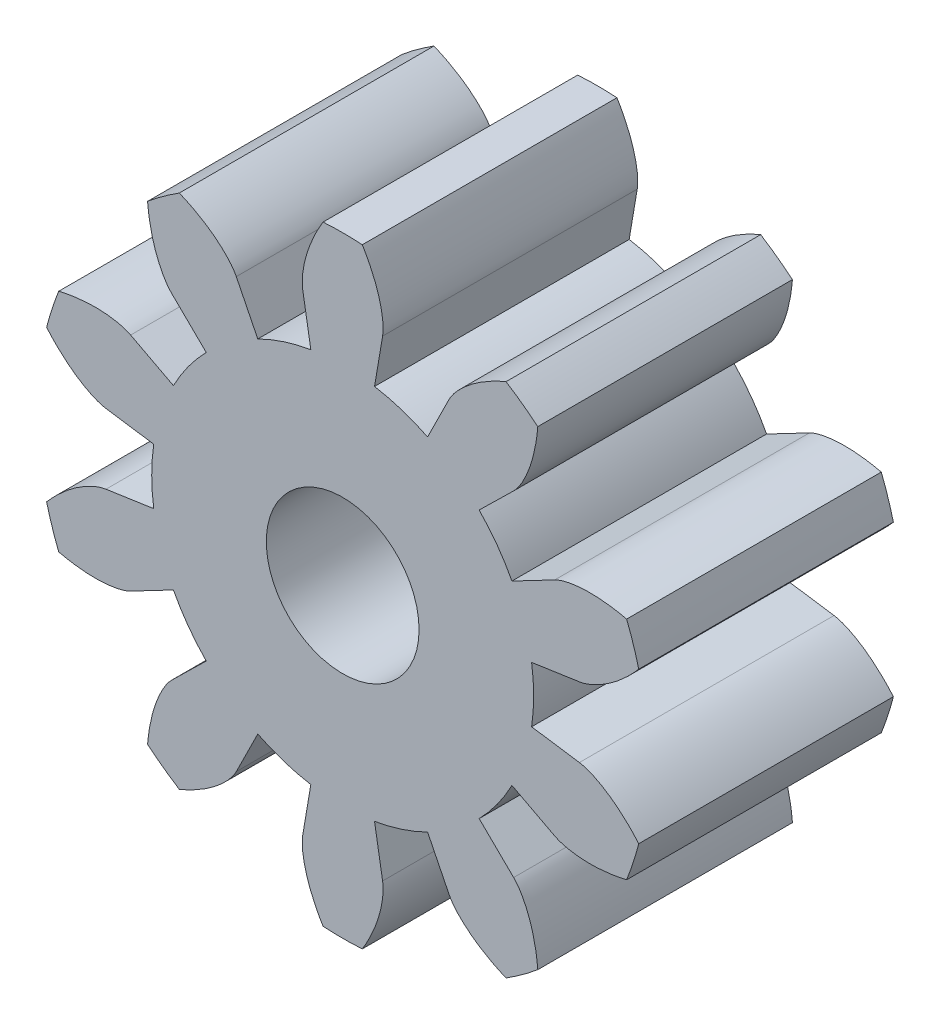
SolidWorks part; units mm, degrees
ref_plane "前视基准面" through (0, 0, 0) normal (0, 0, 1) x (1, 0, 0)
ref_plane "上视基准面" through (0, 0, 0) normal (0, 1, 0) x (1, 0, 0)
ref_plane "右视基准面" through (0, 0, 0) normal (1, 0, 0) x (0, 0, -1)
other "Configuration Table"
sketch "草图1" plane through (0, 0, 0) normal (0, 0, 1) x (1, 0, 0)
  line L0 (0, 0) -> (5, 0) construction
  line L1 (0, 0) -> (4.9384, 0.7822) construction
  line L2 (0, 0) -> (4.6481, 0.6862)
  line L3 (4.9384, 0.7822) -> (4.9384, -0.7822) construction
  line L4 (0, 0) -> (4.6481, -0.6862)
  circle A0 centre (0, 0) radius 6
  circle A1 centre (0, 0) radius 5 construction
  circle A2 centre (0, 0) radius 3.75
  circle A3 centre (0, 0) radius 4.6985 construction
  circle A4 centre (0, 0) radius 1.5
  spline S0 degree 4 poles (4.6481, 0.6862) (4.6835, 0.6914) (4.7813, 0.7134) (4.96, 0.7841) (5.2311, 0.9375) (5.5479, 1.1888) (5.9048, 1.5657) (6.2522, 2.0657) (6.551, 2.6636) (6.8384, 3.517) (6.9822, 4.4081) (6.9969, 5.3449) (6.862, 6.4517) (6.586, 7.5338) (6.0852, 8.7313) (5.3299, 9.9596) (4.4064, 11.0659) (3.3424, 12.0372) (2.1636, 12.8645) (0.8933, 13.5425) (-0.4466, 14.0687) (-1.6629, 14.396) (-2.6365, 14.5668) (-3.3507, 14.6476) (-3.7975, 14.6829) (-4.158, 14.7018) (-4.5134, 14.7121) (-4.8789, 14.7125) (-5.1964, 14.706) (-5.5003, 14.6924) (-5.8676, 14.6691) (-6.1207, 14.6466) (-6.5658, 14.6003) (-6.8589, 14.5561) (-7.1841, 14.508) (-7.4436, 14.4596) (-7.746, 14.4023) (-7.9471, 14.3573) (-8.0927, 14.3246) (-8.163, 14.308) knots 0 0 0 0 0 0.005604 0.015718 0.02996 0.048734 0.068727 0.096889 0.125051 0.153212 0.209535 0.237696 0.271429 0.327752 0.384075 0.440398 0.496721 0.553044 0.609367 0.66569 0.722013 0.778336 0.806497 0.820578 0.834659 0.84874 0.86282 0.876901 0.890982 0.900036 0.909091 0.931818 0.943182 0.954545 0.965909 0.977273 0.988636 1 1 1 1 1 construction
  spline S1 degree 4 poles (4.6481, 0.6862) (4.6835, 0.6914) (4.7813, 0.7134) (4.96, 0.7841) (5.2311, 0.9375) (5.5479, 1.1888) (5.9048, 1.5657) (6.2522, 2.0657) (6.551, 2.6636) (6.8384, 3.517) (6.9822, 4.4081) (6.9969, 5.3449) (6.862, 6.4517) (6.586, 7.5338) (6.0852, 8.7313) (5.3299, 9.9596) (4.4064, 11.0659) (3.3424, 12.0372) (2.1636, 12.8645) (0.8933, 13.5425) (-0.4466, 14.0687) (-1.6629, 14.396) (-2.6365, 14.5668) (-3.3507, 14.6476) (-3.7975, 14.6829) (-4.158, 14.7018) (-4.5134, 14.7121) (-4.8789, 14.7125) (-5.1964, 14.706) (-5.5003, 14.6924) (-5.7156, 14.6787) (-5.8219, 14.671) (-5.8742, 14.6669) knots 0 0 0 0 0 0.005604 0.015718 0.02996 0.048734 0.068727 0.096889 0.125051 0.153212 0.209535 0.237696 0.271429 0.327752 0.384075 0.440398 0.496721 0.553044 0.609367 0.66569 0.722013 0.778336 0.806497 0.820578 0.834659 0.84874 0.86282 0.876901 0.890982 0.900036 0.909091 0.909091 0.909091 0.909091 0.909091
  spline S2 degree 4 poles (4.6481, -0.6862) (4.6835, -0.6914) (4.7813, -0.7134) (4.96, -0.7841) (5.2311, -0.9375) (5.5479, -1.1888) (5.9048, -1.5657) (6.2522, -2.0657) (6.551, -2.6636) (6.8384, -3.517) (6.9822, -4.4081) (6.9969, -5.3449) (6.862, -6.4517) (6.586, -7.5338) (6.0852, -8.7313) (5.3299, -9.9596) (4.4064, -11.0659) (3.3424, -12.0372) (2.1636, -12.8645) (0.8933, -13.5425) (-0.4466, -14.0687) (-1.6629, -14.396) (-2.6365, -14.5668) (-3.3507, -14.6476) (-3.7975, -14.6829) (-4.158, -14.7018) (-4.5134, -14.7121) (-4.8789, -14.7125) (-5.1964, -14.706) (-5.5003, -14.6924) (-5.8676, -14.6691) (-6.1207, -14.6466) (-6.5658, -14.6003) (-6.8589, -14.5561) (-7.1841, -14.508) (-7.4436, -14.4596) (-7.746, -14.4023) (-7.9471, -14.3573) (-8.0927, -14.3246) (-8.163, -14.308) knots 0 0 0 0 0 0.005604 0.015718 0.02996 0.048734 0.068727 0.096889 0.125051 0.153212 0.209535 0.237696 0.271429 0.327752 0.384075 0.440398 0.496721 0.553044 0.609367 0.66569 0.722013 0.778336 0.806497 0.820578 0.834659 0.84874 0.86282 0.876901 0.890982 0.900036 0.909091 0.931818 0.943182 0.954545 0.965909 0.977273 0.988636 1 1 1 1 1 construction
  spline S3 degree 4 poles (4.6481, -0.6862) (4.6835, -0.6914) (4.7813, -0.7134) (4.96, -0.7841) (5.2311, -0.9375) (5.5479, -1.1888) (5.9048, -1.5657) (6.2522, -2.0657) (6.551, -2.6636) (6.8384, -3.517) (6.9822, -4.4081) (6.9969, -5.3449) (6.862, -6.4517) (6.586, -7.5338) (6.0852, -8.7313) (5.3299, -9.9596) (4.4064, -11.0659) (3.3424, -12.0372) (2.1636, -12.8645) (0.8933, -13.5425) (-0.4466, -14.0687) (-1.6629, -14.396) (-2.6365, -14.5668) (-3.3507, -14.6476) (-3.7975, -14.6829) (-4.158, -14.7018) (-4.5134, -14.7121) (-4.8789, -14.7125) (-5.1964, -14.706) (-5.5003, -14.6924) (-5.7156, -14.6787) (-5.8219, -14.671) (-5.8742, -14.6669) knots 0 0 0 0 0 0.005604 0.015718 0.02996 0.048734 0.068727 0.096889 0.125051 0.153212 0.209535 0.237696 0.271429 0.327752 0.384075 0.440398 0.496721 0.553044 0.609367 0.66569 0.722013 0.778336 0.806497 0.820578 0.834659 0.84874 0.86282 0.876901 0.890982 0.900036 0.909091 0.909091 0.909091 0.909091 0.909091
  point P15 (4.9384, 0)
  dimension "齿顶圆直径" = 12
  dimension "分度圆直径" = 10
  dimension "齿根圆直径" = 7.5
  dimension "基圆直径" = 9.3969
  dimension "内孔直径" = 3
  dimension "渐近线镜像线夹角" = 9
extrude "凸台-拉伸1" add sketch "草图1" along normal blind 5 contours A0 | A4
extrude "切除-拉伸1" cut sketch "草图1<3>" along normal through all contours A2 S3 A0 S1 region at (5.04, 0, 0)
sketch "草图1<3>" plane through (0, 0, 0) normal (0, 0, 1) x (1, 0, 0) same geometry as "草图1"
pattern_circular "阵列(圆周)1" count 10 every 36 about axis through (0, 0, 5) along (0, 0, 1) of "切除-拉伸1"
equation "\"m\" = 1'模数"
equation "\"z\" = 10'齿数"
equation "\"a\"= 20度'压力角"
equation "\"d\"= \"m\" * \"z\"'分度圆直径"
equation "\"da\"= ( \"z\" + 2 ) * \"m\"'齿顶圆直径"
equation "\"df\"= ( \"z\" - 2.5 ) * \"m\"'齿根圆直径"
equation "\"s\"= 0.5 * PI * \"m\"'分度圆齿厚"
equation "\"r\"= 0.38 * \"m\"'齿根圆角"
equation "\"B\"= 0.3 * \"d\"'齿厚"
equation "\"db\"= \"m\" * \"z\" * cos ( \"a\" )'基圆直径"
equation "\"rb\"= \"db\" / 2'基圆半径"
equation "\"齿顶圆直径@草图1\"= \"da\""
equation "\"分度圆直径@草图1\"= \"d\""
equation "\"齿根圆直径@草图1\"= \"df\""
equation "\"基圆直径@草图1\"= \"db\""
equation "\"渐近线镜像线夹角@草图1\"= 360 / 4 / \"z\""
equation "\"h\" = 5'齿轮厚度"
equation "\"ir\"= 3'内孔直径"
equation "\"内孔直径@草图1\"= \"ir\""
equation "\"齿轮厚@凸台-拉伸1\"= \"h\""
equation "\"齿轮夹角@阵列(圆周)1\"= 360 / \"z\""
equation "\"齿数@阵列(圆周)1\"= \"z\""
